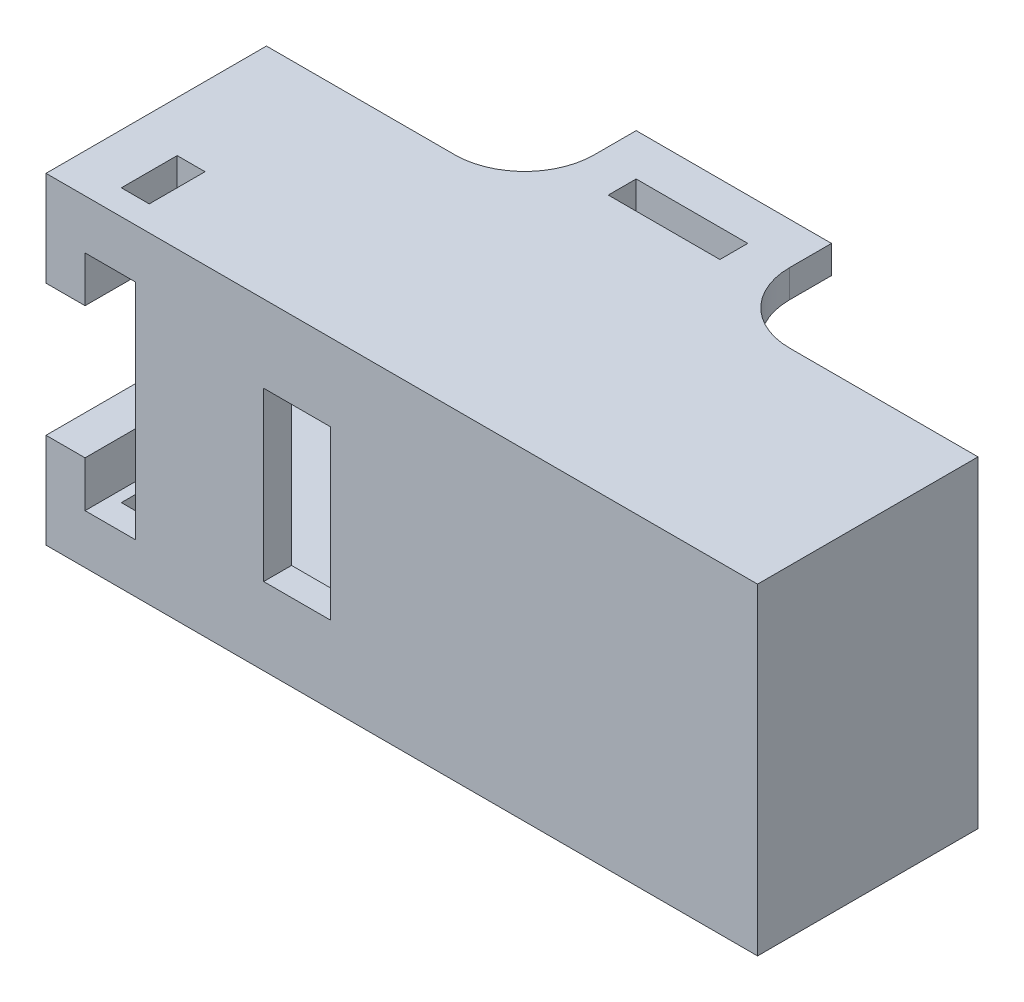
SolidWorks part; units mm, degrees
ref_plane "Face" through (0, 0, 0) normal (0, 0, 1) x (1, 0, 0)
ref_plane "Dessus" through (0, 0, 0) normal (0, 1, 0) x (1, 0, 0)
ref_plane "Droite" through (0, 0, 0) normal (1, 0, 0) x (0, 0, -1)
sketch "Esquisse1" plane through (0, 0, 0) normal (0, 0, 1) x (1, 0, 0)
  line L0 (-9, 0) -> (8, 0) construction
  line L1 (-6.375, 2.885) -> (6.375, 2.885)
  line L2 (-6.375, 2.885) -> (-6.375, -2.885)
  line L3 (-6.375, -2.885) -> (6.375, -2.885)
  line L4 (6.375, 2.885) -> (6.375, -2.885)
  line L5 (0, 5) -> (0, -5) construction
  dimension "D1" = 5.77
  dimension "D2" = 12.75
extrude "Base-Extrusion" add sketch "Esquisse1" along normal blind 5.95
sketch "Esquisse2" plane through (0, 0, 5.95) normal (0, 0, 1) x (1, 0, 0)
  line L0 (0, 0) -> (-6.375, 0) construction
  line L1 (-5.675, 2) -> (-4.775, 2)
  line L2 (-5.675, 2) -> (-5.675, 1.18)
  line L3 (-5.675, -2) -> (-4.775, -2)
  line L4 (-4.775, 2) -> (-4.775, -2)
  line L5 (-6.375, 2.885) -> (-6.375, -2.885) construction
  line L6 (-5.675, 1.18) -> (-6.375, 1.18)
  line L7 (-5.675, -1.18) -> (-6.375, -1.18)
  line L8 (-6.375, 1.18) -> (-6.375, -1.18)
  line L9 (-5.675, -1.18) -> (-5.675, -2)
  dimension "D1" = 0.7
  dimension "D2" = 0.9
  dimension "D3" = 4
  dimension "D4" = 2.36
extrude "Enlèv. mat.-Extru.1" cut sketch "Esquisse2" against normal blind 1.68
shell "Coque1" thickness 0.5 removed face at (0, 0, 0)
sketch "Esquisse3" plane through (0, 0, 0) normal (0, 1, 0) x (1, 0, 0)
  line L0 (6.375, -2) -> (3, -2)
  line L1 (6.375, -5.95) -> (6.375, 0) construction
  line L2 (6.375, 0) -> (-6.375, 0) construction
  line L3 (6.375, 0) -> (1.75, 0)
  line L4 (6.375, -2) -> (6.375, 0)
  line L6 (1.75, 0) -> (1.75, -2) construction
  line L7 (1.75, 0) -> (1.75, -0.75)
  arc A1 (1.75, -0.75) -> (3, -2) centre (3, -0.75) ccw
  dimension "D1" = 2
  dimension "D2" = 1.75
  dimension "D3" = 0.75
extrude "Enlèv. mat.-Extru.2" cut sketch "Esquisse3" against normal through all and the other way through all
mirror "Symétrie1" about plane through (0, 0, 0) normal (1, 0, 0) of "Enlèv. mat.-Extru.2"
sketch "Esquisse4" plane through (0, 0, 0) normal (0, 1, 0) x (1, 0, 0)
  line L0 (0, 0) -> (0, -2.1395) construction
  line L1 (-1, -0.75) -> (1, -0.75)
  line L2 (-1, -0.75) -> (-1, -1.25)
  line L3 (-1, -1.25) -> (1, -1.25)
  line L4 (1, -0.75) -> (1, -1.25)
  line L5 (1.75, 0) -> (-1.75, 0) construction
  line L6 (6.375, -5.95) -> (-6.375, -5.95) construction
  line L7 (-5.475, -4.5) -> (-4.975, -4.5)
  line L8 (-5.475, -4.5) -> (-5.475, -5.5)
  line L9 (-5.475, -5.5) -> (-4.975, -5.5)
  line L10 (-4.975, -4.5) -> (-4.975, -5.5)
  line L11 (-5.225, -4.3615) -> (-5.225, -5.6863) construction
  line L12 (-5.675, -4.27) -> (-5.675, -5.95) construction
  line L13 (-4.775, -4.27) -> (-4.775, -5.95) construction
  dimension "D1" = 2
  dimension "D2" = 0.5
  dimension "D3" = 0.75
  dimension "D4" = 1
  dimension "D5" = 0.5
  dimension "D6" = 0.45
extrude "Enlèv. mat.-Extru.3" cut sketch "Esquisse4" against normal through all and the other way through all
sketch "Esquisse5" plane through (0, 0, 5.95) normal (0, 0, 1) x (1, 0, 0)
  line L0 (0, 0) -> (-2.779, 0) construction
  line L1 (-2.475, 1.5) -> (-1.275, 1.5)
  line L2 (-2.475, 1.5) -> (-2.475, -1.5)
  line L3 (-2.475, -1.5) -> (-1.275, -1.5)
  line L4 (-1.275, 1.5) -> (-1.275, -1.5)
  line L5 (-1.875, 2.6626) -> (-1.875, -2.185) construction
  dimension "D1" = 1.2
  dimension "D2" = 3
  dimension "D3" = 1.875
extrude "Enlèv. mat.-Extru.4" cut sketch "Esquisse5" against normal through all
